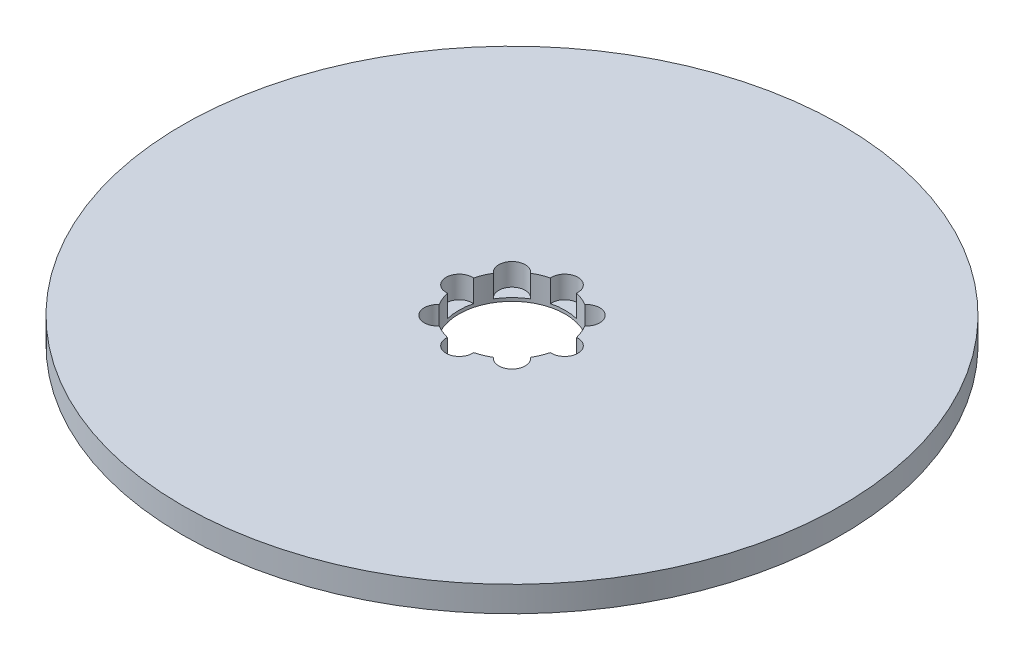
SolidWorks part; units mm, degrees
ref_plane "Front Plane" through (0, 0, 0) normal (0, 0, 1) x (1, 0, 0)
ref_plane "Top Plane" through (0, 0, 0) normal (0, 1, 0) x (1, 0, 0)
ref_plane "Right Plane" through (0, 0, 0) normal (1, 0, 0) x (0, 0, -1)
sketch "Sketch1" plane through (0, 0, 0) normal (0, 1, 0) x (1, 0, 0)
  circle A0 centre (0, 0) radius 77.5
  dimension "FLANGE_OD" = 155
extrude "Boss-Extrude1" add sketch "Sketch1" along normal blind 6
sketch "Sketch2" plane through (0, 0, 0) normal (0, 1, 0) x (1, 0, 0)
  circle A0 centre (0, 0) radius 12.5
  dimension "BORE_D" = 25
extrude "Cut-Extrude1" cut sketch "Sketch2" along normal through all
sketch "Sketch3" plane through (0, 6, 0) normal (0, 1, 0) x (1, 0, 0)
  circle A0 centre (0, 0) radius 12.3911 construction
  circle A1 centre (-12.3911, 0) radius 3.0995
  dimension "BOLT_D" = 6.199
  dimension "BOLT_PCD" = 24.7823
extrude "Cut-Extrude2" cut sketch "Sketch3" against normal blind 5.2284
pattern_circular "CirPattern1" count 8 over 360 about axis through (0, 0, 0) along (0, 1, 0) of "Cut-Extrude2"
